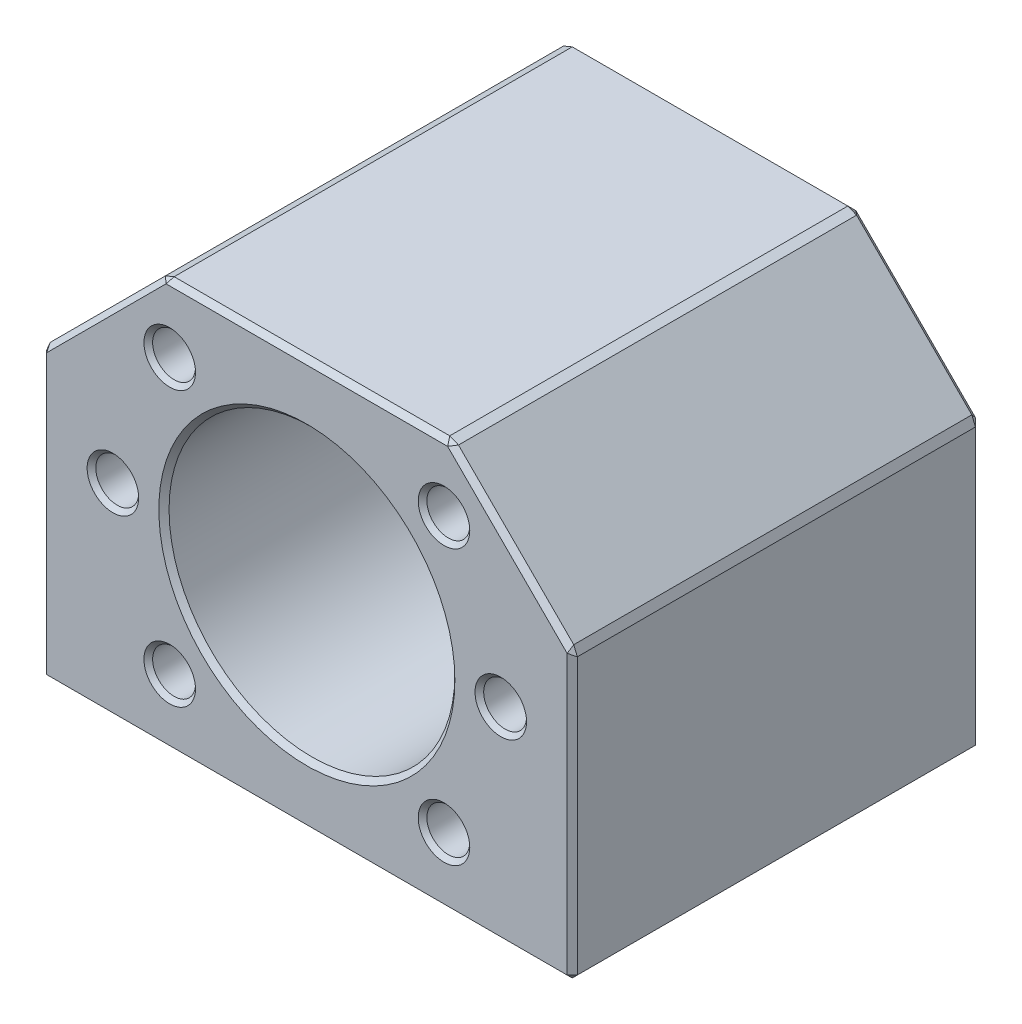
SolidWorks part; units mm, degrees
ref_plane "Front Plane" through (0, 0, 0) normal (0, 0, 1) x (1, 0, 0)
ref_plane "Top Plane" through (0, 0, 0) normal (0, 1, 0) x (1, 0, 0)
ref_plane "Right Plane" through (0, 0, 0) normal (1, 0, 0) x (0, 0, -1)
sketch "Sketch1" plane through (0, 0, 0) normal (0, 0, 1) x (1, 0, 0)
  line L0 (0, 0) -> (0, -20) construction
  line L1 (26, -20) -> (26, 8)
  line L2 (26, 8) -> (14, 20)
  line L3 (-26, -20) -> (-26, 8)
  line L4 (-26, 8) -> (-14, 20)
  line L5 (-14, 20) -> (14, 20)
  line L6 (-26, -20) -> (26, -20)
  circle A0 centre (0, 0) radius 14
  dimension "D2" = 28
  dimension "D1" = 52
  dimension "D3" = 20
  dimension "D4" = 40
  dimension "D5" = 12
  dimension "D6" = 12
extrude "Boss-Extrude1" add sketch "Sketch1" along normal mid plane 40
sketch "Sketch2" plane through (0, 0, 20) normal (0, 0, 1) x (1, 0, 0)
  line L0 (-13.435, -13.435) -> (13.435, 13.435) construction
  line L1 (19, 0) -> (-19, 0) construction
  line L2 (-13.435, 13.435) -> (13.435, -13.435) construction
  line L3 (0, 0) -> (0, -20) construction
  line L4 (-26, -20) -> (26, -20) construction
  circle A0 centre (0, 0) radius 19 construction
  circle A1 centre (13.435, 13.435) radius 2.1 construction
  circle A2 centre (19, 0) radius 2.1 construction
  circle A3 centre (13.435, -13.435) radius 2.1 construction
  circle A4 centre (-13.435, -13.435) radius 2.1 construction
  circle A5 centre (-19, 0) radius 2.1 construction
  circle A6 centre (-13.435, 13.435) radius 2.1 construction
  point P4 (0, 0)
  dimension "D1" = 4.2
  dimension "D3" = 38
  dimension "D2" = 90
sketch "Sketch4" plane through (0, -20, 0) normal (0, -1, 0) x (1, 0, 0)
  line L0 (-26, 20) -> (26, 20) construction
  line L1 (-20, -12) -> (20, -12) construction
  line L2 (-20, -12) -> (-20, 12) construction
  line L3 (-20, 12) -> (20, 12) construction
  line L4 (20, -12) -> (20, 12) construction
  line L5 (0, 12) -> (0, -12) construction
  line L6 (-20, 0) -> (20, 0) construction
  circle A0 centre (20, 12) radius 2.1
  circle A1 centre (20, -12) radius 2.1
  circle A2 centre (-20, -12) radius 2.1
  circle A3 centre (-20, 12) radius 2.1
  point P0 (0, 0)
  dimension "D4" = 4.2
  dimension "D1" = 24
  dimension "D2" = 40
  dimension "D3" = 8
hole_wizard "M5x0.8 Tapped Hole1" positions "3DSketch1" profile "Sketch3" tap size "M5x0.8" standard "ANSI Metric"
sketch3d "3DSketch1"
  point P0 (13.435, 13.435, 20)
  point P3 (19, 0, 20)
  point P6 (13.435, -13.435, 20)
  point P9 (-13.435, -13.435, 20)
  point P12 (-19, 0, 20)
  point P15 (-13.435, 13.435, 20)
  point P19 (20, -20, 12)
  point P22 (20, -20, -12)
  point P25 (-20, -20, -12)
  point P28 (-20, -20, 12)
sketch "Sketch3" plane through (13.435, 13.435, 20) normal (1, 0, 0) x (0, -1, 0)
  line L0 (0, 0) -> (0, 13.6618)
  line L1 (0, 13.6618) -> (2.1, 12.4)
  line L2 (2.1, 12.4) -> (2.1, 0.425)
  line L3 (2.1, 0.425) -> (2.525, 0)
  line L5 (2.525, 0) -> (0, 0)
  line L6 (-2.1, 0.425) -> (-2.525, 0) construction
  line L10 (0, 13.6618) -> (-2.1, 12.4) construction
  line L11 (0, -6.35) -> (0, 107.95) construction
  dimension "Tap Drill Dia." = 4.2
  dimension "Tap Drill Depth" = 12.4
  dimension "Near C'Sink Dia." = 5.05
  dimension "Near C'Sink Angle" = 90
  dimension "Drill Angle" = 118
cosmetic thread "Hole Thread1" parameters "D1"=10, "D2"=5
cosmetic thread "Hole Thread2" parameters "D1"=10, "D2"=5
cosmetic thread "Hole Thread3" parameters "D1"=10, "D2"=5
cosmetic thread "Hole Thread4" parameters "D1"=10, "D2"=5
cosmetic thread "Hole Thread5" parameters "D1"=10, "D2"=5
cosmetic thread "Hole Thread6" parameters "D1"=10, "D2"=5
cosmetic thread "Hole Thread7" parameters "D1"=10, "D2"=5
cosmetic thread "Hole Thread8" parameters "D1"=10, "D2"=5
cosmetic thread "Hole Thread9" parameters "D1"=10, "D2"=5
cosmetic thread "Hole Thread10" parameters "D1"=10, "D2"=5
chamfer "Chamfer1" distance 0.5 20 edges at (14, 0, 20) (-26, 8, 0) (-14, 20, 0) (14, 20, 0) (26, 8, 0) (14, 0, -20) (-26, -20, 0) (26, -6, 20) (20, 14, 20) (0, 20, 20) (-20, 14, 20) (-26, -6, 20) (0, -20, 20) (26, -20, 0) (-20, 14, -20) (-26, -6, -20) (0, -20, -20) (26, -6, -20) (20, 14, -20) (0, 20, -20)
sketch "Sketch5" [suppressed] plane through (0, 0, 20) normal (0, 0, 1) x (1, 0, 0)
  line L0 (26, 7.5) -> (26, -19.5) construction
  line L1 (-27, 21) -> (27, 21)
  line L2 (-27, 21) -> (-27, 14.5)
  line L3 (-27, 14.5) -> (27, 14.5)
  line L4 (27, 21) -> (27, 14.5)
  line L5 (0, 0) -> (0, 14.5) construction
  line L6 (-13.5, 20) -> (13.5, 20) construction
  dimension "D1" = 14.5
  dimension "D2" = 1
  dimension "D3" = 1
extrude "Cut-Extrude1" [suppressed] cut sketch "Sketch5" against normal through all
equation "\"D6@Sketch1\"=\"D5@Sketch1\""
